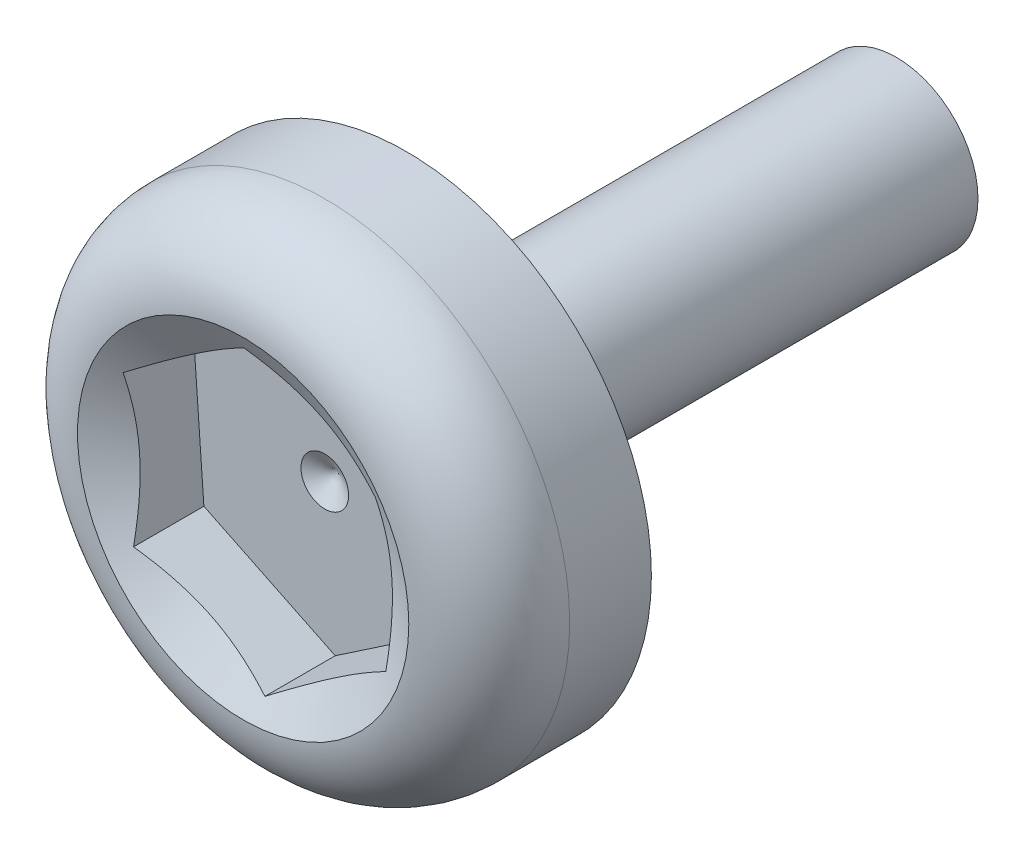
SolidWorks part; units mm, degrees
ref_plane "Front Plane" through (0, 0, 0) normal (0, 0, 1) x (1, 0, 0)
ref_plane "Top Plane" through (0, 0, 0) normal (0, 1, 0) x (1, 0, 0)
ref_plane "Right Plane" through (0, 0, 0) normal (1, 0, 0) x (0, 0, -1)
sketch "Sketch1" plane through (0, 0, 0) normal (0, 0, 1) x (1, 0, 0)
  circle A0 centre (0, 0) radius 0.5
  dimension "D1" = 1
extrude "Boss-Extrude1" add sketch "Sketch1" along normal blind 3
sketch "Sketch2" plane through (0, 0, 3) normal (0, 0, 1) x (1, 0, 0)
  circle A0 centre (0, 0) radius 1.5
  dimension "D1" = 3
extrude "Boss-Extrude2" add sketch "Sketch2" along normal blind 1
sketch "Sketch3" plane through (0, 0, 0) normal (0, 1, 0) x (1, 0, 0)
  line L0 (0, -4) -> (0, -2.6044) construction
  line L1 (-1.5, -4) -> (1.5, -4) construction
  line L2 (0, -3.4159) -> (1.0144, -4)
  line L3 (1.0144, -4) -> (0, -4)
  line L4 (0, -4) -> (0, -3.4159)
revolve "Cut-Revolve1" cut sketch "Sketch3" angle 360 about L4
sketch "Sketch4" plane through (0, 0, 4) normal (0, 0, 1) x (1, 0, 0)
  line L1 (-0.0641, 0.892) -> (-0.8045, 0.3905)
  line L2 (-0.8045, 0.3905) -> (-0.7405, -0.5015)
  line L3 (-0.7405, -0.5015) -> (0.0641, -0.892)
  line L4 (0.0641, -0.892) -> (0.8045, -0.3905)
  line L5 (0.8045, -0.3905) -> (0.7405, 0.5015)
  line L6 (0.7405, 0.5015) -> (-0.0641, 0.892)
  circle A0 centre (0, 0) radius 0.7745 construction
  point P1 (-0.8431, 0.4194)
  point P10 (0.6138, 0.3954)
  point P11 (-0.0641, 0.892)
extrude "Cut-Extrude2" cut sketch "Sketch4" against normal blind 0.5
fillet "Fillet1" radius 0.5 1 edges at (1.5, 0, 4)
